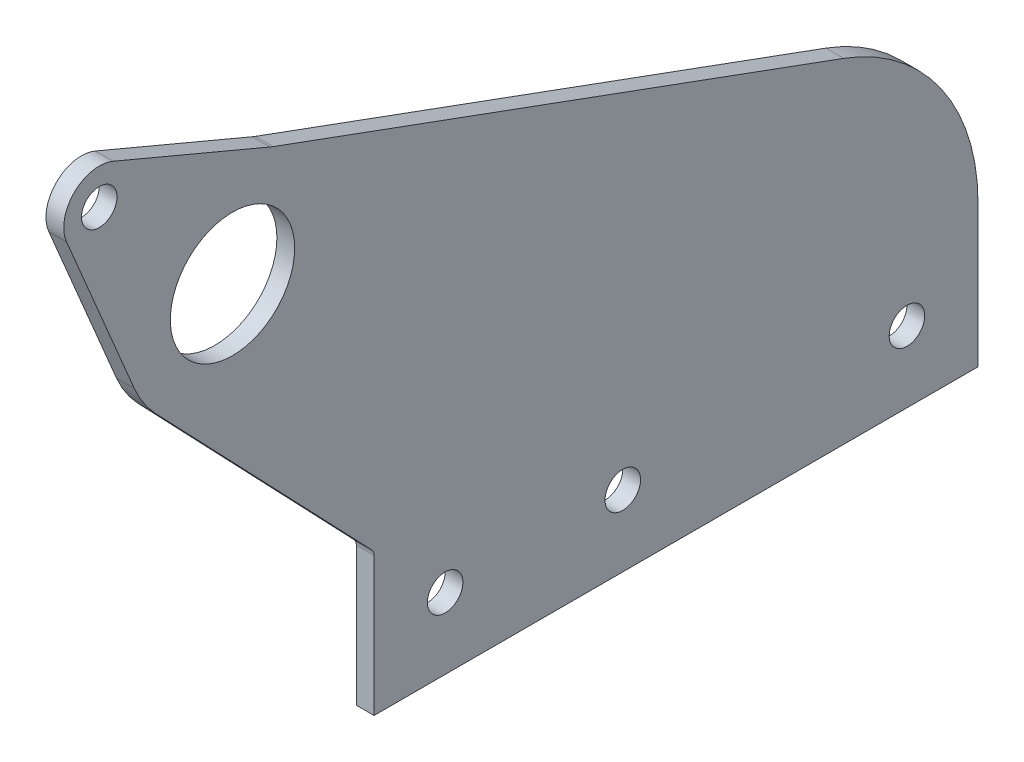
SolidWorks part; units mm, degrees
material "6061-T6 (SS)"
ref_plane "Front Plane" through (0, 0, 0) normal (0, 0, 1) x (1, 0, 0)
ref_plane "Top Plane" through (0, 0, 0) normal (0, 1, 0) x (1, 0, 0)
ref_plane "Right Plane" through (0, 0, 0) normal (1, 0, 0) x (0, 0, -1)
sketch "Sketch1" plane through (0, 0, 0) normal (1, 0, 0) x (0, 0, -1)
  line L0 (0, 0) -> (0, 25.4)
  line L1 (0, 25.4) -> (-39.0852, 66.3014)
  line L2 (-18.7642, 97.3517) -> (177.8, 25.4)
  line L3 (177.8, 25.4) -> (177.8, 0)
  line L4 (177.8, 0) -> (0, 0)
  line L5 (-25.3125, 79.4625) -> (0, 0) construction
  line L6 (-18.9625, 0) -> (261.1995, 0) construction
  line L7 (-18.9625, 0) -> (-18.9625, -60.325) construction
  line L8 (-18.9625, -60.325) -> (261.1995, -60.325) construction
  line L9 (261.1995, 0) -> (261.1995, -60.325) construction
  line L10 (-25.3125, 79.4625) -> (177.8, 0) construction
  arc A0 (-39.0852, 66.3014) -> (-18.7642, 97.3517) centre (-25.3125, 79.4625) cw
  circle A1 centre (-25.3125, 79.4625) radius 11.1125
  dimension "D3" = 22.225
  dimension "D4" = 19.05
  dimension "D1" = 177.8
  dimension "D2" = 25.4
  dimension "D5" = 60.325
  dimension "D6" = 280.162
  dimension "D7" = 6.35
  dimension "D8" = 18.9625
  dimension "D9" = 83.3967
base flange "Base-Flange1" sketch "Sketch1" thickness 3.175 reverse thickness direction no parameters "D1"=0.7366
sketch "Sketch2" plane through (0, 0, 0) normal (1, 0, 0) x (0, 0, -1)
  line L0 (-25.3125, 79.4625) -> (-49.125, 103.275) construction
  line L1 (-49.125, 103.275) -> (-49.125, 55.65) construction
  line L2 (-49.125, 55.65) -> (-25.3125, 79.4625) construction
  line L3 (-46.6597, 109.1269) -> (-18.6163, 97.313)
  line L4 (-54.9769, 100.8098) -> (-42.8683, 72.0667)
  line L7 (177.8, 25.4) -> (-18.7642, 97.3517) construction
  line L8 (-18.0513, 97.0907) -> (-18.7642, 97.3517)
  circle A0 centre (-25.3125, 79.4625) radius 33.676 construction
  circle A1 centre (-49.125, 103.275) radius 3.175
  arc A2 (-54.9769, 100.8098) -> (-46.6597, 109.1269) centre (-49.125, 103.275) cw
  arc A3 (-18.7642, 97.3517) -> (-39.0852, 66.3014) centre (-25.3125, 79.4625) ccw construction
  arc A4 (-18.7642, 97.3517) -> (-42.8683, 72.0667) centre (-25.3125, 79.4625) ccw
  arc A5 (-18.6163, 97.313) -> (-18.0513, 97.0907) centre (-13.6858, 109.0169) ccw
  dimension "D2" = 6.35
  dimension "D3" = 12.7
  dimension "D4" = 6.35
  dimension "D1" = 47.625
base flange "Tab1" sketch "Sketch2" thickness 3.175 reverse thickness direction no parameters "D1"=0.7366
sketch "Sketch3" plane through (-3.175, 0, 0) normal (-1, 0, 0) x (0, 0, 1)
  line L0 (-177.8, 12.7) -> (0, 12.7) construction
  line L1 (0, 25.4) -> (0, 0) construction
  line L3 (0, 0) -> (-177.8, 0) construction
  line L4 (-107.95, 25.4) -> (-107.95, 0)
  line L5 (-177.8, 0) -> (-177.8, 25.4) construction
  line L6 (0, 25.4) -> (0, 0) construction
  line L7 (-177.8, 25.4) -> (18.0513, 97.0907) construction
  line L8 (-83.9397, 59.7573) -> (-177.8, 25.4)
  line L9 (-177.8, 25.4) -> (-177.8, 0)
  line L10 (-177.8, 0) -> (-107.95, 0)
  circle A0 centre (-95.25, 12.7) radius 3.175
  circle A1 centre (-12.7, 12.7) radius 3.175
  arc A2 (-83.9397, 59.7573) -> (-107.95, 25.4) centre (-71.3633, 25.4) ccw
  circle A3 centre (-44.45, 12.7) radius 3.175
  circle A4 centre (-44.45, 12.7) radius 2.6035 construction
  dimension "D1" = 6.35
  dimension "D2" = 12.7
  dimension "D3" = 25.4
  dimension "D4" = 12.7
  dimension "D5" = 69.85
  dimension "D6" = 12.7
extrude "Cut-Extrude1" cut sketch "Sketch3" against normal through all normal cut yes
fillet "Fillet2" [suppressed] radius 18.5952
fillet "Fillet1" radius 1.5875 1 edges at (-1.5875, 25.4, 0)
sketch "Bend-Lines1" [suppressed] plane through (0, 0, 0) normal (0, 1, 0) x (1, 0, 0)
sketch "Bounding-Box1" [suppressed] plane through (0, 0, 0) normal (0, 1, 0) x (1, 0, 0)
sheet metal parameters "Sheet-Metal1" thickness 3.175 parameters "D1"=0.7366
flat pattern "Flat-Pattern1" [suppressed]
sketch "Bend-Lines2" plane through (0, 0, 0) normal (0, 1, 0) x (1, 0, 0)
sketch3d "Bounding-Box2" [suppressed]
  line L0 (185.463, -132.628, 0) -> (-33.3012, -60.0044, 0) construction
  line L1 (210.7124, -56.5692, 0) -> (-8.0518, 16.0545, 0) construction
  line L2 (185.463, -132.628, 0) -> (210.7124, -56.5692, 0) construction
  line L3 (-33.3012, -60.0044, 0) -> (-8.0518, 16.0545, 0) construction
sheet metal parameters "Sheet-Metal2" thickness 3.175 parameters "D1"=0.7366
flat pattern "Flat-Pattern2"
sketch "Bend-Lines3" plane through (0, 0, 0) normal (0, 1, 0) x (1, 0, 0)
sketch3d "Bounding-Box3" [suppressed]
  line L0 (181.3924, -137.6868, 0) -> (-57.5803, -48.5401, 0) construction
  line L1 (211.4302, -57.1654, 0) -> (-27.5425, 31.9813, 0) construction
  line L2 (181.3924, -137.6868, 0) -> (211.4302, -57.1654, 0) construction
  line L3 (-57.5803, -48.5401, 0) -> (-27.5425, 31.9813, 0) construction
sheet metal parameters "Sheet-Metal3" thickness 3.175 parameters "D1"=0.7366
flat pattern "Flat-Pattern2"
sketch "Bend-Lines3" plane through (0, 0, 0) normal (0, 1, 0) x (1, 0, 0)
sketch3d "Bounding-Box3" [suppressed]
  line L0 (119.7639, -115.1692, 0) -> (-57.7697, -48.0539, 0) construction
  line L1 (150.0267, -35.1176, 0) -> (-27.5068, 31.9976, 0) construction
  line L2 (119.7639, -115.1692, 0) -> (150.0267, -35.1176, 0) construction
  line L3 (-57.7697, -48.0539, 0) -> (-27.5068, 31.9976, 0) construction
